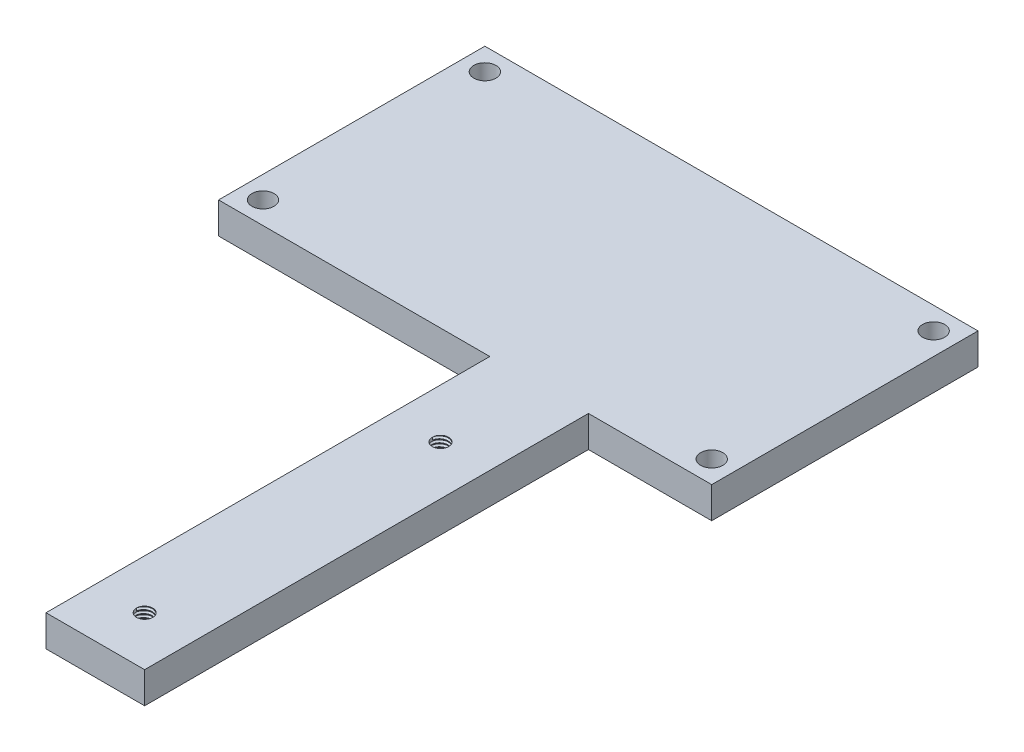
SolidWorks part; units mm, degrees
ref_plane "Front Plane" through (0, 0, 0) normal (0, 0, 1) x (1, 0, 0)
ref_plane "Top Plane" through (0, 0, 0) normal (0, 1, 0) x (1, 0, 0)
ref_plane "Right Plane" through (0, 0, 0) normal (1, 0, 0) x (0, 0, -1)
sketch "Sketch1" plane through (0, 0, 0) normal (0, 1, 0) x (1, 0, 0)
  line L0 (0, -55) -> (0, 55) construction
  line L2 (-50, -27) -> (-50, 27)
  line L3 (-50, 27) -> (50, 27)
  line L4 (50, -27) -> (50, 27)
  line L5 (-50, -27) -> (50, 27) construction
  line L6 (-50, 27) -> (50, -27) construction
  line L7 (45.5, -22.5) -> (-45.5, -22.5) construction
  line L8 (45.5, -22.5) -> (45.5, 22.5) construction
  line L9 (45.5, 22.5) -> (-45.5, 22.5) construction
  line L10 (-45.5, -22.5) -> (-45.5, 22.5) construction
  line L11 (45.5, -22.5) -> (-45.5, 22.5) construction
  line L12 (45.5, 22.5) -> (-45.5, -22.5) construction
  line L13 (-55, 0) -> (55, 0) construction
  line L14 (15, -117) -> (15, -107) construction
  line L17 (25, -117) -> (5, -117)
  line L19 (15, -107) -> (15, -47) construction
  line L20 (15, -47) -> (15, -27) construction
  line L21 (25, -117) -> (25, -27)
  line L22 (5, -117) -> (5, -27)
  line L23 (25, -27) -> (15, -27) construction
  line L26 (5, -27) -> (15, -27) construction
  line L28 (5, -27) -> (-50, -27)
  line L29 (25, -27) -> (50, -27)
  circle A0 centre (-45.5, 22.5) radius 2.25
  circle A1 centre (45.5, 22.5) radius 2.25
  circle A2 centre (45.5, -22.5) radius 2.25
  circle A3 centre (-45.5, -22.5) radius 2.25
  circle A4 centre (15, -47) radius 1.65
  circle A5 centre (15, -107) radius 1.65
  point P0 (0, 0)
  point P6 (0, 0)
  dimension "D3" = 4.5
  dimension "D10" = 3.3
  dimension "D11" = 3.3
  dimension "D2" = 100
  dimension "D4" = 91
  dimension "D5" = 45
  dimension "D6" = 60
  dimension "D7" = 10
  dimension "D8" = 20
  dimension "D9" = 20
  dimension "D12" = 54
  dimension "D13" = 35
extrude "Boss-Extrude1" add sketch "Sketch1" along normal blind 3.175 and the other way blind 3.175
thread "Thread1" pitch 0.7 method cut profile "Thread Profile1" start angle 0, offset 0, length 10, pitch 0.7, diameter 3.3
ref_plane "Plane1" through (13.35, 3.175, 47) normal (0, 0, 1) x (-1, 0, 0)
sketch "Thread Profile1" plane through (13.35, 3.175, 47) normal (0, 0, 1) x (-1, 0, 0)
  line L0 (0, 0) -> (0, 0.7) construction
  line L1 (0, 0) -> (0.3789, 0.2187)
  line L2 (0.3789, 0.2187) -> (0.3789, 0.3062)
  line L3 (0.3789, 0.3062) -> (0, 0.525)
  line L4 (0.3789, 0.2625) -> (0, 0.2625) construction
  line L11 (0, 0) -> (0, 0.525)
  point P2 (0, 0)
  dimension "Pitch" = 0.7
  dimension "Profile_Angle" = 60
  dimension "Profile_Land" = 0.0875
  dimension "Profile_Height" = 0.3789
thread "Thread2" pitch 0.7 method cut profile "Thread Profile2" start angle 0, offset 0, length 10, pitch 0.7, diameter 3.3
ref_plane "Plane2" through (13.35, 3.175, 107) normal (0, 0, 1) x (-1, 0, 0)
sketch "Thread Profile2" plane through (13.35, 3.175, 107) normal (0, 0, 1) x (-1, 0, 0)
  line L0 (0, 0) -> (0, 0.7) construction
  line L1 (0, 0) -> (0.3789, 0.2187)
  line L2 (0.3789, 0.2187) -> (0.3789, 0.3062)
  line L3 (0.3789, 0.3062) -> (0, 0.525)
  line L4 (0.3789, 0.2625) -> (0, 0.2625) construction
  line L11 (0, 0) -> (0, 0.525)
  point P2 (0, 0)
  dimension "Pitch" = 0.7
  dimension "Profile_Angle" = 60
  dimension "Profile_Land" = 0.0875
  dimension "Profile_Height" = 0.3789
